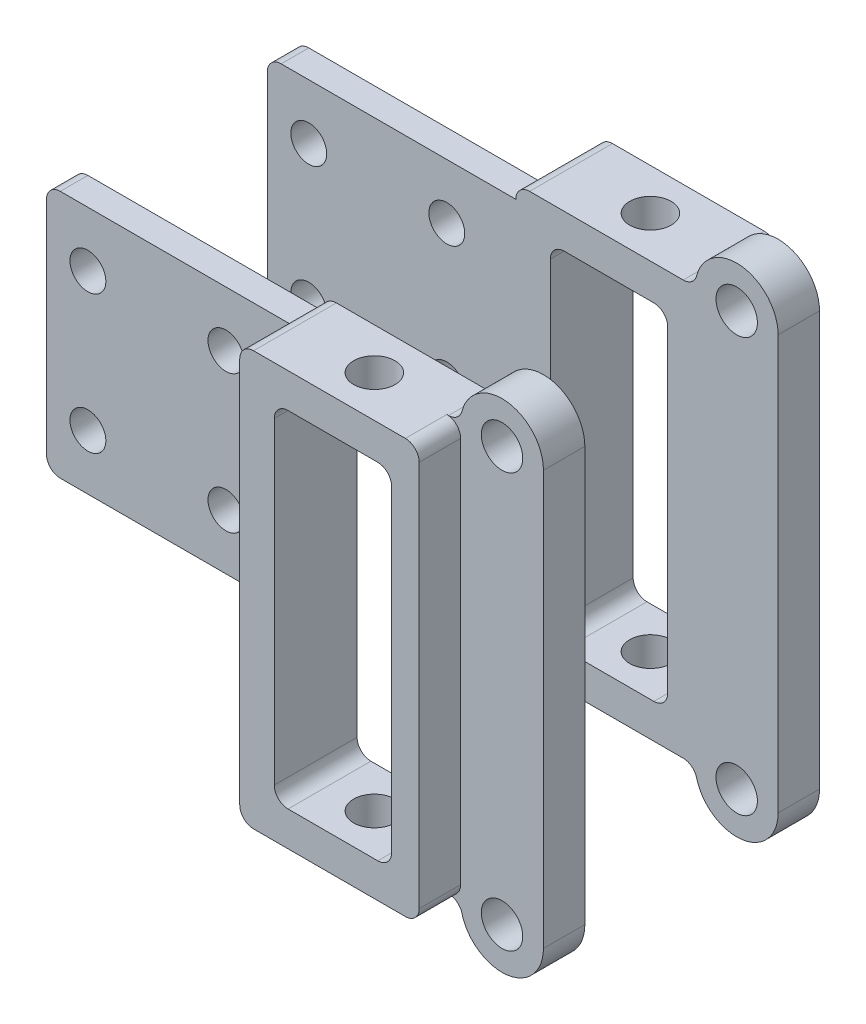
SolidWorks part; units mm, degrees
material "6061-T6 (SS)"
ref_plane "前视基准面" through (0, 0, 0) normal (0, 0, 1) x (1, 0, 0)
ref_plane "上视基准面" through (0, 0, 0) normal (0, 1, 0) x (1, 0, 0)
ref_plane "右视基准面" through (0, 0, 0) normal (1, 0, 0) x (0, 0, -1)
sketch "草图1" plane through (0, 0, 0) normal (0, 0, 1) x (1, 0, 0)
  line L0 (-30, 9) -> (30, 9) construction
  line L1 (-30, -10) -> (30, -10)
  line L2 (-30, -10) -> (-30, 10)
  line L3 (-30, 10) -> (30, 10)
  line L4 (30, -10) -> (30, 10)
  line L5 (-30, -10) -> (30, 10) construction
  line L6 (-30, 10) -> (30, -10) construction
  line L7 (0, -25) -> (60, -25)
  line L8 (0, -25) -> (0, 15)
  line L9 (0, 15) -> (60, 15)
  line L10 (60, -25) -> (60, 15)
  line L11 (0, -25) -> (60, 15) construction
  line L12 (0, 15) -> (60, -25) construction
  line L13 (0, 14) -> (60, 14) construction
  line L14 (-30, -9) -> (30, -9) construction
  line L15 (0, -24) -> (60, -24) construction
  point P0 (0, 0)
  point P6 (30, -5)
  dimension "D1" = 20
  dimension "D2" = 60
  dimension "D3" = 60
  dimension "D4" = 5
  dimension "D5" = 40
  dimension "D6" = 1
  dimension "D7" = 1
  dimension "D8" = 1
  dimension "D9" = 1
sketch "草图2" plane through (0, 0, 0) normal (0, 0, 1) x (1, 0, 0)
  line L2 (0, 14) -> (60, 14) construction
  line L3 (30, -10) -> (30, 10) construction
  line L4 (0, -24) -> (60, -24) construction
  line L5 (49, 10) -> (49, -20)
  line L6 (43, -20) -> (30, -20)
  line L7 (30, -20) -> (30, -9)
  line L8 (30, -9) -> (12, -9)
  line L9 (-30, -9) -> (30, -9) construction
  line L10 (12, -9) -> (12, 9)
  line L11 (-30, 9) -> (30, 9) construction
  line L12 (12, 9) -> (30, 9)
  line L13 (30, 9) -> (30, 10)
  line L14 (30, 10) -> (43, 10)
  line L15 (-30, -10) -> (30, -10) construction
  line L16 (-30, 10) -> (30, 10) construction
  circle A0 centre (46, 10) radius 4 construction
  circle A1 centre (46, 10) radius 1.5
  circle A2 centre (46, 10) radius 3 construction
  circle A3 centre (46, -20) radius 4 construction
  circle A4 centre (46, -20) radius 1.5
  circle A5 centre (46, -20) radius 3 construction
  arc A6 (43, 10) -> (49, 10) centre (46, 10) cw
  arc A7 (49, -20) -> (43, -20) centre (46, -20) cw
  circle A8 centre (25, 5) radius 1.3
  circle A9 centre (25, -5) radius 1.3
  circle A10 centre (15, 5) radius 1.3
  circle A11 centre (15, -5) radius 1.3
  dimension "D1" = 8
  dimension "D2" = 16
  dimension "D3" = 3
  dimension "D4" = 6
  dimension "D5" = 8
  dimension "D6" = 3
  dimension "D7" = 6
  dimension "D8" = 5
  dimension "D9" = 5
  dimension "D10" = 5
  dimension "D11" = 5
  dimension "D13" = 2.6
  dimension "D14" = 10
  dimension "D15" = 10
  dimension "D12" = 18
extrude "凸台-拉伸1" add sketch "草图2" along normal blind 2
sketch "草图3" plane through (0, 0, 2) normal (0, 0, 1) x (1, 0, 0)
  line L0 (30, -20) -> (30, 10)
  line L1 (30, 10) -> (43, 10)
  line L2 (30, -20) -> (43, -20)
  line L3 (49, 10) -> (49, -20)
  arc A0 (43, 10) -> (49, 10) centre (46, 10) cw
  arc A1 (49, -20) -> (43, -20) centre (46, -20) cw
  circle A2 centre (46, 10) radius 1.5
  circle A3 centre (46, -20) radius 1.5
  dimension "D1" = 3
  dimension "D2" = 3
  dimension "D3" = 3
extrude "凸台-拉伸2" add sketch "草图3" along normal blind 4
sketch "草图4" plane through (0, 0, 6) normal (0, 0, 1) x (1, 0, 0)
  line L0 (30, -10) -> (30, 10) construction
  line L1 (32.5, 7.5) -> (41, 7.5)
  line L2 (32.5, 7.5) -> (32.5, -17.5)
  line L3 (32.5, -17.5) -> (41, -17.5)
  line L4 (41, 7.5) -> (41, -17.5)
  line L5 (43, 10) -> (30, 10) construction
  line L6 (30, -20) -> (43, -20) construction
  dimension "D1" = 8.5
  dimension "D2" = 2.5
  dimension "D3" = 2.5
  dimension "D4" = 2.5
extrude "切除-拉伸1" cut sketch "草图4" against normal blind 34
sketch "草图7" plane through (0, 10, 0) normal (0, 1, 0) x (1, 0, 0)
  line L0 (30, -6) -> (30, 0) construction
  line L1 (0, 0) -> (60, 0) construction
  circle A0 centre (36.75, -3) radius 1.5
  dimension "D1" = 6.75
  dimension "D2" = 3
  dimension "D3" = 3
extrude "切除-拉伸2" cut sketch "草图7" against normal blind 34
sketch "草图8" plane through (0, 0, 6) normal (0, 0, 1) x (1, 0, 0)
  line L0 (43, 10) -> (43, -20)
  line L1 (43, 10) -> (30, 10) construction
  line L2 (30, -20) -> (43, -20) construction
  line L3 (41, -17.5) -> (41, 7.5) construction
  line L4 (49, 10) -> (49, -20)
  arc A0 (43, 10) -> (49, 10) centre (46, 10) cw
  arc A1 (49, -20) -> (43, -20) centre (46, -20) cw
  dimension "D1" = 2
extrude "切除-拉伸3" cut sketch "草图8" against normal blind 3
fillet "圆角1" radius 1 6 edges at (12, 9, 1) (12, -9, 1) (43, -20, 4.5) (30, -20, 3) (30, 10, 3) (43, 10, 4.5)
sketch "草图9" plane through (0, 0, 2) normal (0, 0, 1) x (1, 0, 0)
  line L0 (-30, 9) -> (30, 9) construction
  line L1 (-30, -9) -> (30, -9) construction
  circle A0 centre (28.75, 9) radius 1.25
  circle A1 centre (28.75, -9) radius 1.25
  dimension "D1" = 2.5
  dimension "D2" = 2.5
extrude "切除-拉伸4" [suppressed] cut sketch "草图9" against normal blind 3
fillet "圆角2" radius 1 2 edges at (43, 10, 1.5) (43, -20, 1.5)
fillet "圆角3" radius 1 4 edges at (41, 7.5, 3) (41, -17.5, 3) (32.5, -17.5, 3) (32.5, 7.5, 3)
ref_plane "基准面4" through (0, 0, -7) normal (0, 0, -1) x (-1, 0, 0)
mirror "镜向2" about plane through (0, 0, -7) normal (0, 0, -1) of bodies 105 106
